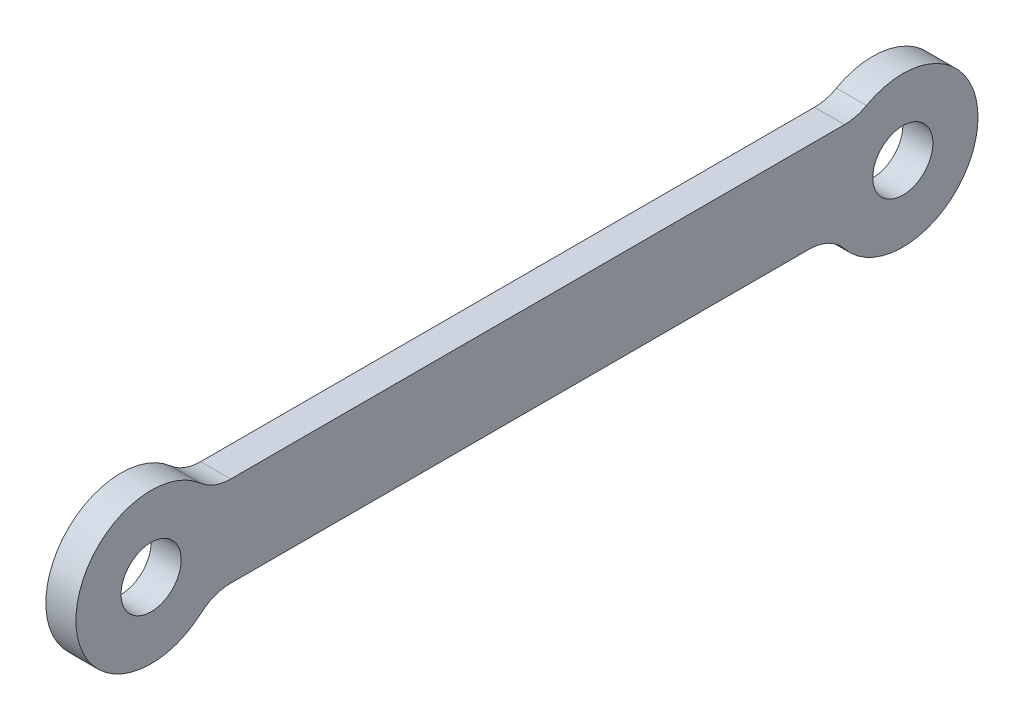
SolidWorks part; units mm, degrees
ref_plane "前视基准面" through (0, 0, 0) normal (0, 0, 1) x (1, 0, 0)
ref_plane "上视基准面" through (0, 0, 0) normal (0, 1, 0) x (1, 0, 0)
ref_plane "右视基准面" through (0, 0, 0) normal (1, 0, 0) x (0, 0, -1)
other "Configuration Table"
sketch "草图1" plane through (0, 0, 0) normal (1, 0, 0) x (0, 0, -1)
  line L1 (0, -3) -> (50, -3)
  line L2 (0, -3) -> (0, 3)
  line L3 (0, 3) -> (50, 3)
  line L4 (50, -3) -> (50, 3)
  circle A0 centre (0, 0) radius 5
  circle A1 centre (50, -1) radius 5
  circle A2 centre (0, 0) radius 2
  circle A3 centre (50, -1) radius 2
  point P12 (0, 0)
  point P13 (0, 0)
  point P14 (0, 0)
  point P16 (0, 0)
  dimension "D1" = 4
  dimension "D4" = 10
  dimension "D5" = 10
  dimension "D2" = 6
  dimension "D3" = 2
  dimension "D6" = 50
extrude "凸台-拉伸1" add sketch "草图1" along normal blind 2 contours A0 | L3 L4 L1 L2 | A1
extrude "切除-拉伸2" cut sketch "草图1<3>" against normal through all and the other way through all contours A2 | A3
sketch "草图1<3>" plane through (0, 0, 0) normal (1, 0, 0) x (0, 0, -1) same geometry as "草图1"
fillet "圆角1" radius 3 4 edges at (1, -3, -4) (1, -3, -45.4174) (1, 3, -47) (1, 3, -4)
